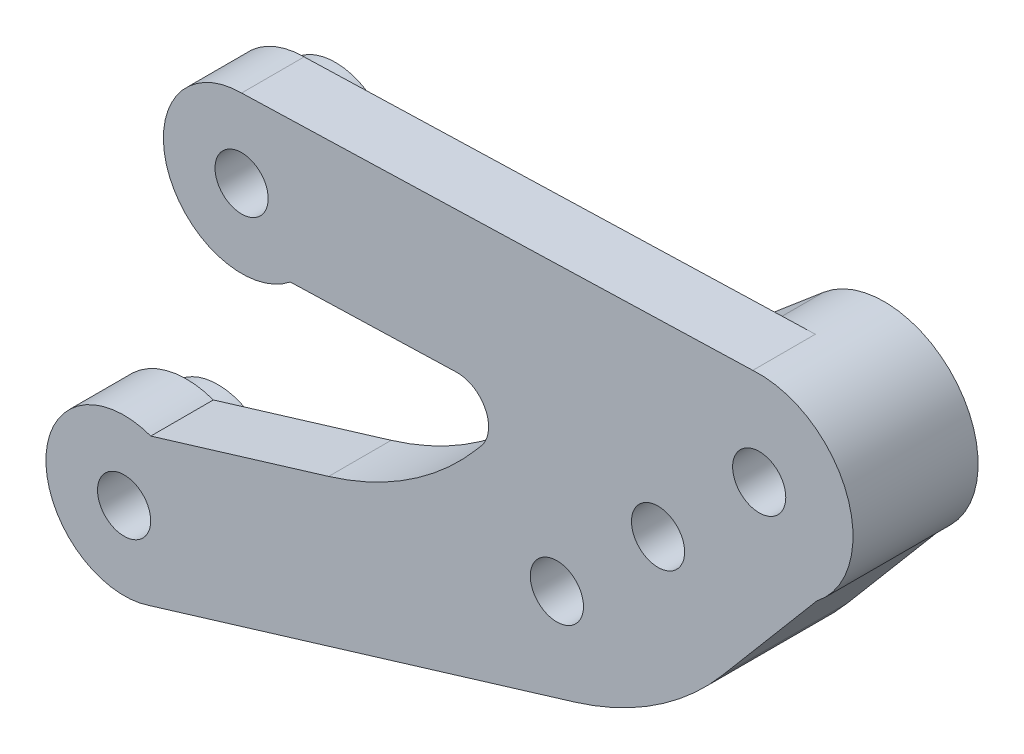
SolidWorks part; units mm, degrees
ref_plane "Front Plane" through (0, 0, 0) normal (0, 0, 1) x (1, 0, 0)
ref_plane "Top Plane" through (0, 0, 0) normal (0, 1, 0) x (1, 0, 0)
ref_plane "Right Plane" through (0, 0, 0) normal (1, 0, 0) x (0, 0, -1)
sketch "Sketch2" plane through (0, 0, 0) normal (0, 0, 1) x (1, 0, 0)
  line L0 (0, 0) -> (0, 21.6008) construction
  line L1 (40.6129, 21.6008) -> (0, 21.6008) construction
  line L2 (0, 0) -> (0, 21.6008) construction
  line L3 (0, 21.6008) -> (7.5129, 21.6008) construction
  line L4 (1.5758, -4.7452) -> (34.4569, 5.2326)
  line L5 (34.4569, 5.2326) -> (44.2966, 16.8647)
  line L6 (7.5129, 26.6008) -> (40.2038, 27.5868)
  line L10 (25.7338, 18.1463) -> (18.7287, 9.8651)
  line L11 (18.7287, 9.8651) -> (1.7066, 4.6997)
  line L12 (10.6292, 17.6907) -> (25.7338, 18.1463)
  circle A0 centre (0, 0) radius 1.7
  circle A1 centre (40.6129, 21.6008) radius 1.7
  circle A2 centre (7.5129, 21.6008) radius 1.7
  arc A3 (1.7066, 4.6997) -> (1.5758, -4.7452) centre (0, 0) ccw
  arc A4 (44.2966, 16.8647) -> (40.2038, 27.5868) centre (40.6129, 21.6008) ccw
  arc A5 (7.5129, 26.6008) -> (10.6292, 17.6907) centre (7.5129, 21.6008) ccw
  dimension "D1" = 3.4
  dimension "D2" = 3.4
  dimension "D3" = 3.4
  dimension "D8" = 10
  dimension "D9" = 12
  dimension "D10" = 10
  dimension "D4" = 46
  dimension "D5" = 33.1
  dimension "D7" = 22.87
  dimension "D11" = 9
  dimension "D12" = 9
  dimension "D13" = 15
extrude "Boss-Extrude1" add sketch "Sketch2" along normal blind 2 and the other way blind 2 contours L6 A5 A3 L4 L5 A4 A0 A1 A2 region at (22.1673, 13.7132, 0)
fillet "Fillet1" radius 20 2 edges at (34.4569, 5.2326, 0) (18.7287, 9.8651, 0)
sketch "Sketch3" plane through (0, 0, 2) normal (0, 0, 1) x (1, 0, 0)
  line L0 (44.2966, 16.8647) -> (30.687, 0.776)
  line L1 (38.2697, 9.7399) -> (44.2966, 16.8647) construction
  line L2 (30.687, 0.776) -> (37.0794, -4.6314)
  line L3 (37.0794, -4.6314) -> (43.0769, 2.4586)
  line L4 (44.2966, 16.8647) -> (50.689, 11.4573)
  line L5 (50.689, 11.4573) -> (44.6915, 4.3673)
  line L6 (43.0769, 2.4586) -> (32.5644, 0.4977)
  line L7 (32.5644, 0.4977) -> (44.8824, 15.0595)
  line L8 (44.8824, 15.0595) -> (44.6915, 4.3673)
  line L9 (32.5644, 0.4977) -> (31.9186, -0.2658) construction
  line L10 (44.8824, 15.0595) -> (45.5282, 15.8229) construction
  dimension "D1" = 1
  dimension "D2" = 2.5
extrude "Boss-Extrude2" [suppressed] add sketch "Sketch3" against normal up to surface (10 mm away)
fillet "Fillet2" [suppressed] radius 1
sketch "Sketch4" plane through (0, 0, 2) normal (0, 0, 1) x (1, 0, 0)
  line L7 (38.2697, 9.7399) -> (44.2966, 16.8647) construction
  line L8 (0, 0) -> (50000, 0) construction
  line L17 (44.2966, 16.8647) -> (44.8756, 15.9348)
  line L18 (40.6475, 27.6007) -> (47.8271, 27.6007)
  line L19 (47.8271, 27.6007) -> (51.8229, 19.889)
  line L20 (51.0994, 17.0478) -> (51.7638, 16.0989)
  line L21 (48.2447, 15.0489) -> (48.9091, 14.1)
  line L22 (48.3535, 17.9314) -> (-28630.4683, 40975.5336) construction
  arc A0 (40.6475, 27.6007) -> (44.2966, 16.8647) centre (40.6129, 21.6008) cw
  arc A1 (44.2966, 16.8647) -> (40.2038, 27.5868) centre (40.6129, 21.6008) ccw construction
  arc A3 (48.2447, 15.0489) -> (51.0994, 17.0478) centre (48.2713, 18.0488) ccw
  arc A4 (44.8756, 15.9348) -> (51.7638, 16.0989) centre (48.2713, 18.0488) ccw
  arc A5 (48.9091, 14.1) -> (51.8229, 19.889) centre (48.2713, 18.0488) ccw
  dimension "D1" = 6
  dimension "D2" = 8
  dimension "D3" = 55
extrude "Boss-Extrude3" [suppressed] add sketch "Sketch4" against normal up to surface (4 mm away)
fillet "Fillet3" [suppressed] radius 6
sketch "Sketch7" plane through (0, 0, 2) normal (0, 0, -1) x (-1, 0, 0)
  line L0 (-38.2697, 9.7399) -> (-44.2966, 16.8647) construction
  line L1 (-1.5758, -4.7452) -> (-28.8077, 3.5184) construction
  line L2 (-36.7334, 26.1779) -> (-21.684, 13.4222)
  line L4 (-44.2966, 16.8647) -> (-38.2697, 9.7399)
  line L6 (-40.6129, 21.6008) -> (-26.9361, 9.686) construction
  arc A2 (-38.2697, 9.7399) -> (-28.8077, 3.5184) centre (-23.0001, 22.6566) ccw
  arc A3 (-36.7334, 26.1779) -> (-44.2966, 16.8647) centre (-40.6129, 21.6008) ccw
  arc A4 (-28.8077, 3.5184) -> (-21.684, 13.4222) centre (-26.9361, 9.686) ccw
  arc A5 (-22.5414, 14.3724) -> (-13.0794, 8.1508) centre (-7.2719, 27.2891) ccw construction
  circle A6 centre (-40.6129, 21.6008) radius 1.7
  arc A7 (-40.2038, 27.5868) -> (-44.2966, 16.8647) centre (-40.6129, 21.6008) ccw construction
  point P5 (-33.0604, 15.194)
  point P21 (-28.8077, 3.5184)
extrude "Boss-Extrude4" add sketch "Sketch7" against normal blind 4
sketch "Sketch8" plane through (0, 0, 2) normal (0, 0, -1) x (-1, 0, 0)
  circle A0 centre (-7.5129, 21.6008) radius 1.7
  circle A1 centre (-7.5129, 21.6008) radius 3.7
  circle A2 centre (0, 0) radius 1.7
  circle A3 centre (0, 0) radius 3.7
  dimension "D1" = 2
  dimension "D2" = 2
  dimension "D3" = 3.4
  dimension "D4" = 3.4
extrude "Boss-Extrude5" add sketch "Sketch8" against normal blind 2
fillet "Fillet4" radius 2 1 edges at (25.7338, 18.1463, 0)
sketch "Sketch9" plane through (0, 0, 6) normal (0, 0, 1) x (1, 0, 0)
  line L0 (40.6129, 21.6008) -> (26.9361, 9.686) construction
  circle A0 centre (33.8268, 15.689) radius 1.7
  arc A2 (21.684, 13.4222) -> (28.8077, 3.5184) centre (26.9361, 9.686) ccw construction
  circle A3 centre (27.0407, 9.7772) radius 1.7
  dimension "D1" = 3.4
  dimension "D2" = 3.4
  dimension "D3" = 9
  dimension "D4" = 9
extrude "Cut-Extrude1" [suppressed] cut sketch "Sketch9" against normal through all
mirror "Mirror1" [suppressed] of bodies 106
delete or keep bodies "Body-Delete/Keep 1" [suppressed] type delete bodies bodies 107 106
mirror "Mirror2" [suppressed] of bodies 106
delete or keep bodies "Body-Delete/Keep 2" [suppressed] type delete bodies bodies 106
hole_wizard "Ø1.5mm Dowel Hole1" positions "Sketch14" profile "Sketch15" hole size "Ø1.5" standard "ANSI Metric" end condition through all
sketch "Sketch14" plane through (0, 0, 6) normal (0, 0, 1) x (1, 0, 0)
  point P3 (34.1438, 15.3437)
  point P6 (27.6747, 9.0867)
sketch "Sketch15" plane through (34.1438, 15.3437, 6) normal (1, 0, 0) x (0, -1, 0)
  line L0 (0, 0) -> (0, 8)
  line L1 (0, 8) -> (1.7, 8)
  line L2 (1.7, 8) -> (1.7, 0)
  line L5 (1.7, 0) -> (0, 0)
  line L11 (0, -6.35) -> (0, 107.95) construction
  dimension "Thru Hole Dia." = 3.4
  dimension "Thru Hole Depth" = 8
mirror "Mirror3" about plane through (0, 0, -2) normal (0, 0, 1) of bodies 110
delete or keep bodies "Body-Delete/Keep 3" type delete bodies bodies 110
